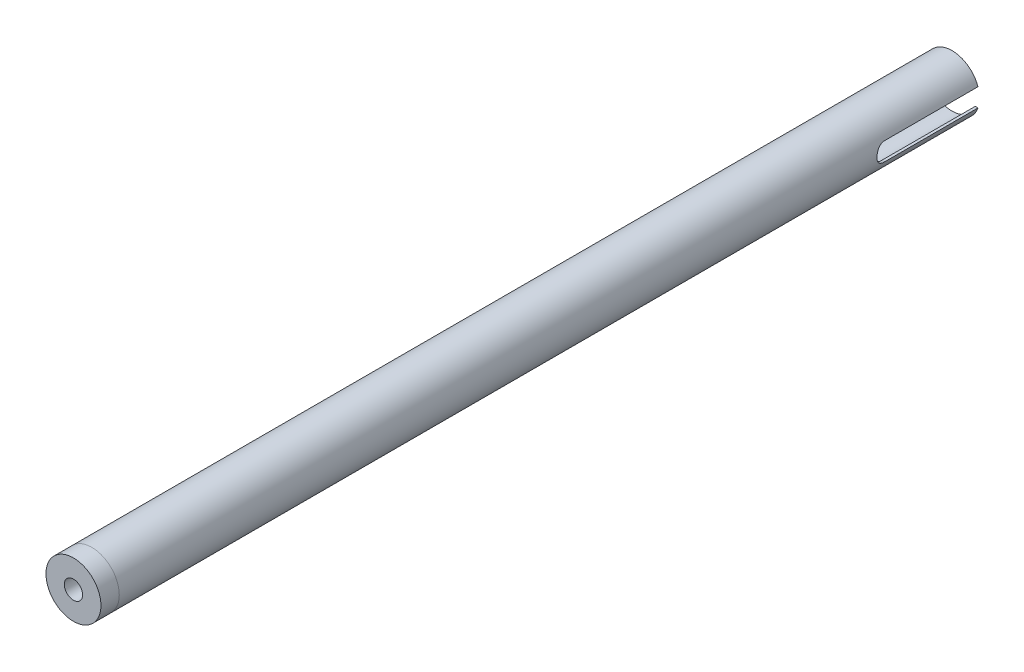
SolidWorks part; units mm, degrees
material "AISI 4130 Steel, normalized at 870C"
ref_plane "Front Plane" through (0, 0, 0) normal (0, 0, 1) x (1, 0, 0)
ref_plane "Top Plane" through (0, 0, 0) normal (0, 1, 0) x (1, 0, 0)
ref_plane "Right Plane" through (0, 0, 0) normal (1, 0, 0) x (0, 0, -1)
sketch "Axis" plane through (0, 0, 0) normal (0, 1, 0) x (1, 0, 0)
  line L0 (0, 0) -> (0, 304.3801) construction
  line L1 (0, 0) -> (0, -21.9075) construction
  line L2 (0, 304.3801) -> (-9.525, 304.3801) construction
  line L3 (0, 332.3201) -> (-22.1542, 267.3343) construction
  dimension "D1" = 21.9075
  dimension "D2" = 9.525
sketch "Sketch1" plane through (0, 0, 0) normal (0, 0, 1) x (1, 0, 0)
  line L0 (-9.525, 0) -> (9.525, 0) construction
  line L1 (-8.9803, 3.175) -> (8.9803, 3.175)
  line L2 (-8.9803, -3.175) -> (8.9803, -3.175)
  circle A0 centre (0, 0) radius 9.525
  circle A1 centre (0, 0) radius 8.636
  circle A2 centre (0, 0) radius 3.175
  dimension "D1" = 19.05
  dimension "D3" = 6.35
  dimension "D2" = 0.889
  dimension "D4" = 6.35
extrude "Threaded insert 1-1" add sketch "Sketch1" against normal blind 6.35 contours A2 L1 A1 | A1 L1 A0 | A2 L0 A1 L1 | A1 L0 A0 L1 | L0 A1 L2 A0 | L0 A2 L2 A1 | A2 L2 A1 | A1 L2 A0 | L0 A1 L2 A2 | L0 A0 L2 A1 | A0 L0 A1 L1 | A1 L0 A2 L1 region at (5.4259, 1.6615, 0) region at (5.4259, -1.6615, 0) region at (8.8881, 1.6046, 0) region at (8.8881, -1.6046, 0) region at (-5.4259, -1.6615, 0) region at (-5.4259, 1.6615, 0) region at (0, 5.4321, 0) region at (0, -5.4321, 0) region at (0, 8.8265, 0) region at (8.5057, -3.3655, 0) region at (-8.8881, -1.6046, 0) region at (-8.8881, 1.6046, 0)
extrude "Threaded insert 1-2" add sketch "Sketch1<3>" against normal blind 6.35 from surface contours A2 L1 A1 | A2 L0 A1 L1 | L0 A2 L2 A1 | A2 L2 A1 | L0 A1 L2 A2 | A1 L0 A2 L1 region at (5.4259, 1.6615, 0) region at (5.4259, -1.6615, 0) region at (-5.4259, -1.6615, 0) region at (-5.4259, 1.6615, 0) region at (0, 5.4321, 0) region at (0, -5.4321, 0) starting at face at (9.525, 0, -6.35)
sketch "Sketch1<3>" plane through (0, 0, 0) normal (0, 0, 1) x (1, 0, 0) same geometry as "Sketch1"
extrude "A-arm tube" add sketch "Sketch1<4>" against normal up to vertex (304.3801 mm away) from surface separate body contours A1 L1 A0 | A1 L0 A0 L1 | L0 A1 L2 A0 | A1 L2 A0 | L0 A0 L2 A1 | A0 L0 A1 L1 region at (8.8881, 1.6046, 0) region at (8.8881, -1.6046, 0) region at (0, 8.8265, 0) region at (8.5057, -3.3655, 0) region at (-8.8881, -1.6046, 0) region at (-8.8881, 1.6046, 0) up to point (0, 0, -304.3801) starting at face at (8.636, 0, -6.35)
sketch "Sketch1<4>" plane through (0, 0, 0) normal (0, 0, 1) x (1, 0, 0) same geometry as "Sketch1"
extrude "Apex slot" cut sketch "Sketch1<5>" along normal blind 35.56 from surface contours A0 L0 A1 L1 | L0 A0 L2 A1 | A1 L0 A0 L1 | L0 A1 L2 A0 region at (8.8881, 1.6046, 0) region at (8.8881, -1.6046, 0) region at (-8.8881, -1.6046, 0) region at (-8.8881, 1.6046, 0) starting at face at (8.636, 0, -304.3801)
sketch "Sketch1<5>" plane through (0, 0, 0) normal (0, 0, 1) x (1, 0, 0) same geometry as "Sketch1"
fillet "Fillet1" radius 3.175 4 edges at (-8.5057, 3.175, -268.8201) (-8.5057, -3.175, -268.8201) (8.5057, -3.175, -268.8201) (8.5057, 3.175, -268.8201)
equation "\"tube diameter\"= 3 / 4"
equation "\"tube thickness\"= .035"
equation "\"apex thickness\"= .25"
equation "\"tube slot\"= 1.4"
equation "\"D1@Sketch1\"=\"tube diameter\""
equation "\"D2@Sketch1\"=\"tube thickness\""
equation "\"threaded insert hole\"= 1 / 4"
equation "\"D3@Sketch1\"=\"threaded insert hole\""
equation "\"D4@Sketch1\"=\"apex thickness\""
equation "\"D1@Apex slot\" = \"tube slot\""
equation "\"D1@Fillet1\"=\"apex thickness\"/2"
equation "\"D2@Axis\"=\"tube diameter\"/2"
